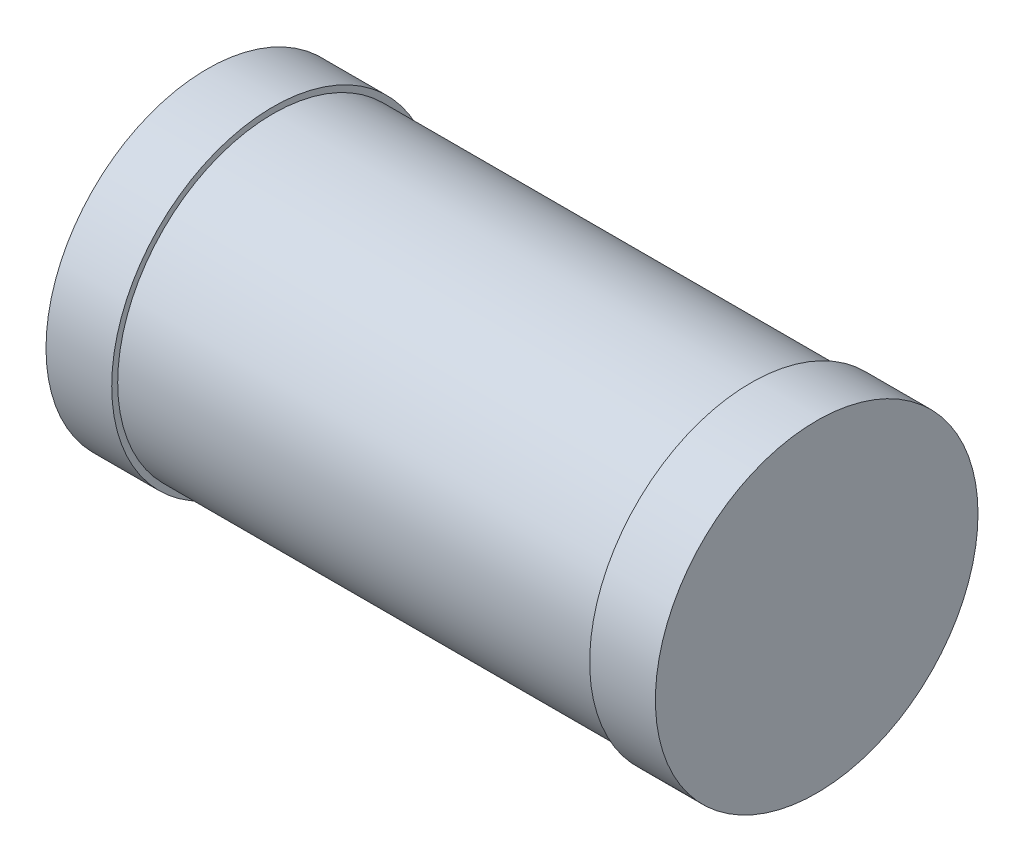
SolidWorks part; units mm, degrees
ref_plane "Спереди" through (0, 0, 0) normal (0, 0, 1) x (1, 0, 0)
ref_plane "Сверху" through (0, 0, 0) normal (0, 1, 0) x (1, 0, 0)
ref_plane "Справа" through (0, 0, 0) normal (1, 0, 0) x (0, 0, -1)
sketch "Эскиз1" plane through (0, 0, 0) normal (1, 0, 0) x (0, 0, -1)
  circle A0 centre (0, 0) radius 1.3
extrude "Бобышка-Вытянуть1" add sketch "Эскиз1" along normal blind 2.5 and the other way blind 2.5
sketch "Эскиз6" plane through (2.5, 0, 0) normal (1, 0, 0) x (0, 0, -1)
  circle A0 centre (0, 0) radius 1.35
extrude "Бобышка-Вытянуть3" add sketch "Эскиз6" against normal blind 0.5 and the other way blind 0.05
sketch "Эскиз8" plane through (-2.5, 0, 0) normal (-1, 0, 0) x (0, 0, 1)
  circle A0 centre (0, 0) radius 1.35
extrude "Бобышка-Вытянуть4" add sketch "Эскиз8" against normal blind 0.5 and the other way blind 0.05
